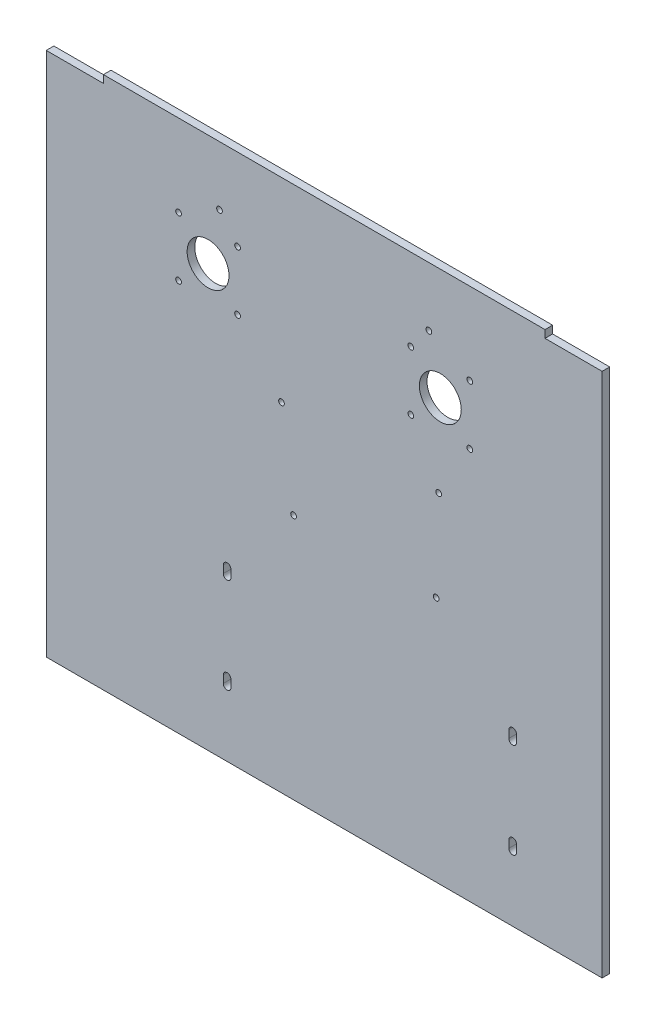
SolidWorks part; units mm, degrees
ref_plane "Front Plane" through (0, 0, 0) normal (0, 0, 1) x (1, 0, 0)
ref_plane "Top Plane" through (0, 0, 0) normal (0, 1, 0) x (1, 0, 0)
ref_plane "Right Plane" through (0, 0, 0) normal (1, 0, 0) x (0, 0, -1)
sketch "Sketch1" plane through (0, 0, 0) normal (0, 0, 1) x (1, 0, 0)
  line L0 (-45.5, 82.5) -> (-76.5, 82.5) construction
  line L1 (146, -123.5) -> (-146, -123.5)
  line L2 (146, -123.5) -> (146, 123.5)
  line L3 (146, 123.5) -> (-146, 123.5)
  line L4 (-146, -123.5) -> (-146, 123.5)
  line L5 (146, -123.5) -> (-146, 123.5) construction
  line L6 (146, 123.5) -> (-146, -123.5) construction
  line L7 (-45.5, 82.5) -> (-45.5, 113.5) construction
  line L8 (-45.5, 113.5) -> (-76.5, 113.5) construction
  line L9 (-76.5, 82.5) -> (-76.5, 113.5) construction
  line L10 (-45.5, 82.5) -> (-76.5, 113.5) construction
  line L11 (-45.5, 113.5) -> (-76.5, 82.5) construction
  line L12 (0, 123.5) -> (0, -133.2191) construction
  line L13 (45.5, 113.5) -> (76.5, 82.5) construction
  line L14 (45.5, 82.5) -> (76.5, 113.5) construction
  line L15 (76.5, 82.5) -> (76.5, 113.5) construction
  line L16 (45.5, 113.5) -> (76.5, 113.5) construction
  line L17 (45.5, 82.5) -> (45.5, 113.5) construction
  line L18 (45.5, 82.5) -> (76.5, 82.5) construction
  line L19 (-175.5662, 125.5) -> (218.0802, 125.5) construction
  line L20 (-146, 123.5) -> (146, 123.5)
  line L21 (-146, 123.5) -> (-146, 156.5)
  line L22 (-146, 156.5) -> (146, 156.5)
  line L23 (146, 123.5) -> (146, 156.5)
  line L24 (0, 156.5) -> (0, 123.5) construction
  line L25 (-146, 140) -> (146, 140) construction
  line L26 (146, 154.5) -> (116, 154.5) construction
  line L27 (-146, 156.5) -> (-116, 156.5)
  line L28 (-146, 156.5) -> (-146, 152.5)
  line L29 (-146, 152.5) -> (-116, 152.5)
  line L30 (-116, 156.5) -> (-116, 152.5)
  line L31 (-131, 152.5) -> (-131, 156.5) construction
  line L32 (-146, 154.5) -> (-116, 154.5) construction
  line L33 (131, 152.5) -> (131, 156.5) construction
  line L34 (116, 156.5) -> (116, 152.5)
  line L35 (146, 152.5) -> (116, 152.5)
  line L36 (146, 156.5) -> (146, 152.5)
  line L37 (146, 156.5) -> (116, 156.5)
  line L38 (-51, -39) -> (-51, -35.0783) construction
  line L39 (-53, -39) -> (-53, -35.0783)
  line L40 (-49, -39) -> (-49, -35.0783)
  line L41 (-51, -89) -> (-51, -85.0783) construction
  line L42 (-53, -89) -> (-53, -85.0783)
  line L43 (-49, -89) -> (-49, -85.0783)
  line L44 (99, -39) -> (99, -35.0783) construction
  line L45 (97, -39) -> (97, -35.0783)
  line L46 (101, -39) -> (101, -35.0783)
  line L47 (99, -89) -> (99, -85.0783) construction
  line L48 (97, -89) -> (97, -85.0783)
  line L49 (101, -89) -> (101, -85.0783)
  circle A0 centre (-76.5, 113.5) radius 1.5
  circle A1 centre (-45.5, 113.5) radius 1.5
  circle A2 centre (76.5, 82.5) radius 1.5
  circle A3 centre (-61, 98) radius 11
  circle A4 centre (-45.5, 82.5) radius 1.5
  circle A5 centre (-76.5, 82.5) radius 1.5
  circle A6 centre (45.5, 82.5) radius 1.5
  circle A7 centre (61, 98) radius 11
  circle A8 centre (45.5, 113.5) radius 1.5
  circle A9 centre (76.5, 113.5) radius 1.5
  circle A10 centre (99, -39) radius 2 construction
  circle A11 centre (99, -89) radius 2 construction
  circle A12 centre (-51, -39) radius 2 construction
  circle A13 centre (-51, -89) radius 2 construction
  circle A14 centre (60.1213, 54.1951) radius 1.5
  circle A15 centre (-55, 125.5) radius 1.5
  circle A16 centre (-16.0787, 5.9351) radius 1.5
  circle A17 centre (58.8513, 5.9351) radius 1.5
  circle A18 centre (-22.4287, 54.1951) radius 1.5
  circle A19 centre (55, 125.5) radius 1.5
  arc A20 (-53, -39) -> (-49, -39) centre (-51, -39) ccw
  arc A21 (-49, -35.0783) -> (-53, -35.0783) centre (-51, -35.0783) ccw
  arc A22 (97, -39) -> (101, -39) centre (99, -39) ccw
  arc A23 (-53, -89) -> (-49, -89) centre (-51, -89) ccw
  arc A24 (-49, -85.0783) -> (-53, -85.0783) centre (-51, -85.0783) ccw
  arc A25 (101, -35.0783) -> (97, -35.0783) centre (99, -35.0783) ccw
  arc A26 (97, -89) -> (101, -89) centre (99, -89) ccw
  arc A27 (101, -85.0783) -> (97, -85.0783) centre (99, -85.0783) ccw
  point P0 (0, 0)
  point P63 (131, 154.5)
  point P65 (-51, -37.0392)
  point P73 (-51, -87.0392)
  point P79 (99, -37.0392)
  point P86 (99, -87.0392)
  point P132 (-131, 154.5)
  point P274 (0, 140)
  dimension "D3" = 22
  dimension "D5" = 3
  dimension "D6" = 85
  dimension "D8" = 3
  dimension "D9" = 3
  dimension "D10" = 3
  dimension "D11" = 2
  dimension "D12" = 2
  dimension "D13" = 2
  dimension "D14" = 2
  dimension "D19" = 3
  dimension "D20" = 3
  dimension "D21" = 3
  dimension "D22" = 3
  dimension "D31" = 3
  dimension "D35" = 2
  dimension "D1" = 292
  dimension "D2" = 247
  dimension "D4" = 31
  dimension "D7" = 10
  dimension "D15" = 95
  dimension "D16" = 150
  dimension "D17" = 50
  dimension "D18" = 34.5
  dimension "D23" = 82.55
  dimension "D24" = 48.26
  dimension "D25" = 74.93
  dimension "D26" = 48.26
  dimension "D27" = 69.3049
  dimension "D28" = 85.8787
  dimension "D29" = 33
  dimension "D30" = 2
  dimension "D32" = 55
  dimension "D33" = 30
  dimension "D34" = 4
extrude "Boss-Extrude1" add sketch "Sketch1" along normal blind 4 contours L4 L1 L2 L3 A18 A17 A16 A14 A13 A12 A11 A10 A8 A6 A5 A4 A3 A0 A1 A2 A7 A9 | L3 L23 L22 L21 region at (-0.0461, -1.0382, 0) region at (0, 139.6509, 0)
